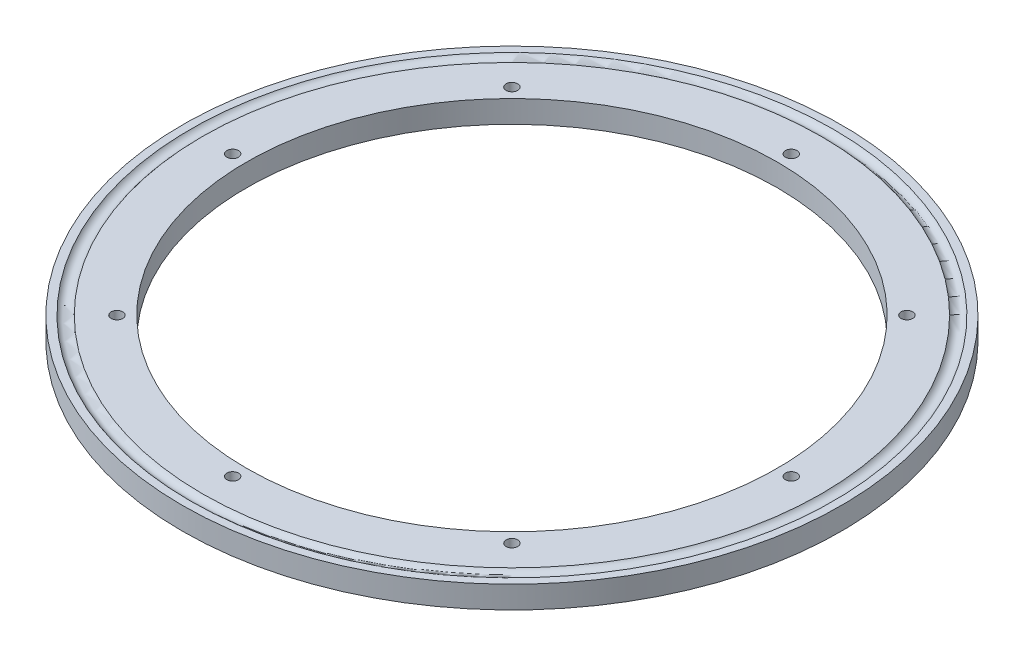
SolidWorks part; units mm, degrees
material "6061 Alloy"
ref_plane "Front Plane" through (0, 0, 0) normal (0, 0, 1) x (1, 0, 0)
ref_plane "Top Plane" through (0, 0, 0) normal (0, 1, 0) x (1, 0, 0)
ref_plane "Right Plane" through (0, 0, 0) normal (1, 0, 0) x (0, 0, -1)
sketch "Sketch1" plane through (0, 0, 0) normal (0, 1, 0) x (1, 0, 0)
  circle A0 centre (0, 0) radius 60.325
  circle A1 centre (0, 0) radius 74.93
  circle A2 centre (0, 0) radius 71.755
  circle A3 centre (0, -63.5) radius 1.3208
  circle A4 centre (-44.9013, -44.9013) radius 1.3208
  circle A5 centre (-63.5, 0) radius 1.3208
  circle A6 centre (-44.9013, 44.9013) radius 1.3208
  circle A7 centre (0, 63.5) radius 1.3208
  circle A8 centre (44.9013, 44.9013) radius 1.3208
  circle A9 centre (63.5, 0) radius 1.3208
  circle A10 centre (44.9013, -44.9013) radius 1.3208
  point P21 (0, 0)
  dimension "D1" = 120.65
  dimension "D4" = 2.6416
  dimension "D5" = 63.5
  dimension "D2" = 14.605
  dimension "D3" = 11.43
  dimension "D6" = 8
extrude "Boss-Extrude1" add sketch "Sketch1" along normal blind 5.08 contours A2 A0 | A1 A2 region at (-72.8107, 0, 0) region at (-69.7255, 0, 0)
sketch "Sketch2" plane through (0, 0, 0) normal (1, 0, 0) x (0, 0, -1)
  line L0 (-74.93, 0) -> (74.93, 0) construction
  line L1 (74.93, 5.08) -> (-74.93, 5.08) construction
  line L2 (-74.93, 0) -> (74.93, 0)
  line L3 (74.93, 5.08) -> (-74.93, 5.08)
  line L4 (89.5975, 4.318) -> (99.9841, 4.318) construction
  line L5 (95.9885, 2.54) -> (99.6739, 2.54) construction
  line L6 (0, 0) -> (0, 18.217) construction
  circle A0 centre (71.755, 5.9055) radius 1.5875 construction
  circle A1 centre (71.755, 5.969) radius 1.651
  circle A2 centre (71.755, -0.889) radius 1.651
  dimension "D3" = 3.175
  dimension "D4" = 3.302
  dimension "D1" = 71.755
  dimension "D2" = 0.762
  dimension "D5" = 2.54
revolve "Cut-Revolve1" cut sketch "Sketch2" angle 360 about L6 region at (0, 0.3118, -71.755) region at (0, 4.7682, -71.755)
equation "\"Middle Coupler Inner Daimeter\"= 4.75in"
equation "\"Middle Coupler  Wall Thickness\" = 0.25in"
equation "\"Middle Coupler Bottom Thickness\"= 0.2in"
equation "\"Bearing Rail Offset\"= 0.45in"
equation "\"3-56 UNF Tap\"= 0.089in"
equation "\"3-56 UNF Clearance\"= 0.104in"
equation "\"D5@Sketch1\"=(\"Middle Coupler Inner Daimeter\"*2+0.5)/4in"
equation "\"Ball Bearing Distance\"= 0.03in"
equation "\"D1@Sketch2\"=\"Middle Coupler Inner Daimeter\"/2+\"Bearing Rail Offset\""
equation "\"D3@Sketch1\"=\"Bearing Rail Offset\""
equation "\"D4@Sketch1\"=\"3-56 UNF Clearance\""
equation "\"D1@Sketch1\"=\"Middle Coupler Inner Daimeter\""
equation "\"D2@Sketch2\"=\"Ball Bearing Distance\""
equation "\"D4@Sketch2\"=\"D3@Sketch2\"+0.005"
equation "\"D5@Sketch2\"=\"Middle Coupler Bottom Thickness\"/2"
equation "\"TCA Outer Diameter\" = 6.625in"
equation "\"Interstage Aeroframe Wall Thickness\" = 0.072in"
equation "\"Compression Spring OD\"= 0.42in"
equation "\"10-24 Tap\"= 0.157in"
equation "\"10-24 Clearance\"= 0.196in"
equation "\"Lower Stage Fuselage Wall Thickness\" = 0.25in"
equation "\"6-32 Tap\" = 0.107in"
equation "\"1/4-20 Tap\" = 0.201in"
